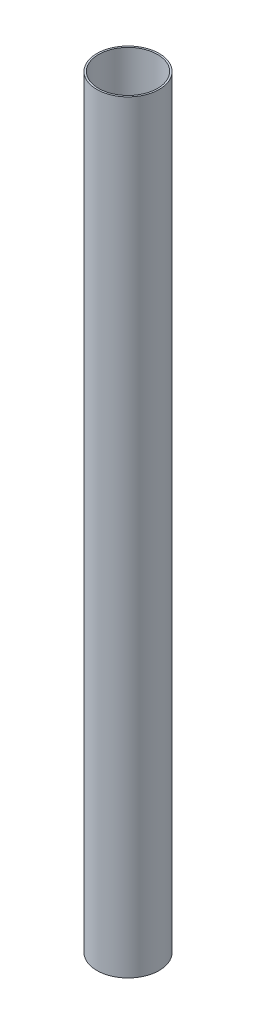
SolidWorks part; units mm, degrees
material "6063-T6"
ref_plane "Front Plane" through (0, 0, 0) normal (0, 0, 1) x (1, 0, 0)
ref_plane "Top Plane" through (0, 0, 0) normal (0, 1, 0) x (1, 0, 0)
ref_plane "Right Plane" through (0, 0, 0) normal (1, 0, 0) x (0, 0, -1)
sketch "Sketch1" plane through (0, 0, 0) normal (0, 0, 1) x (1, 0, 0)
  line L0 (0, 0) -> (0, 45.6531) construction
  line L1 (25.5143, 40.261) -> (26.9875, 40.261)
  line L2 (25.5143, 40.261) -> (25.5143, -620.139)
  line L3 (25.5143, -620.139) -> (26.9875, -620.139)
  line L4 (26.9875, 40.261) -> (26.9875, -620.139)
  point P5 (25.5143, 40.261)
  point P10 (26.9875, 40.261)
  point P12 (26.9875, -618.4626)
  point P13 (26.9875, -620.139)
revolve "Revolve1" add sketch "Sketch1" angle 360 about L0
